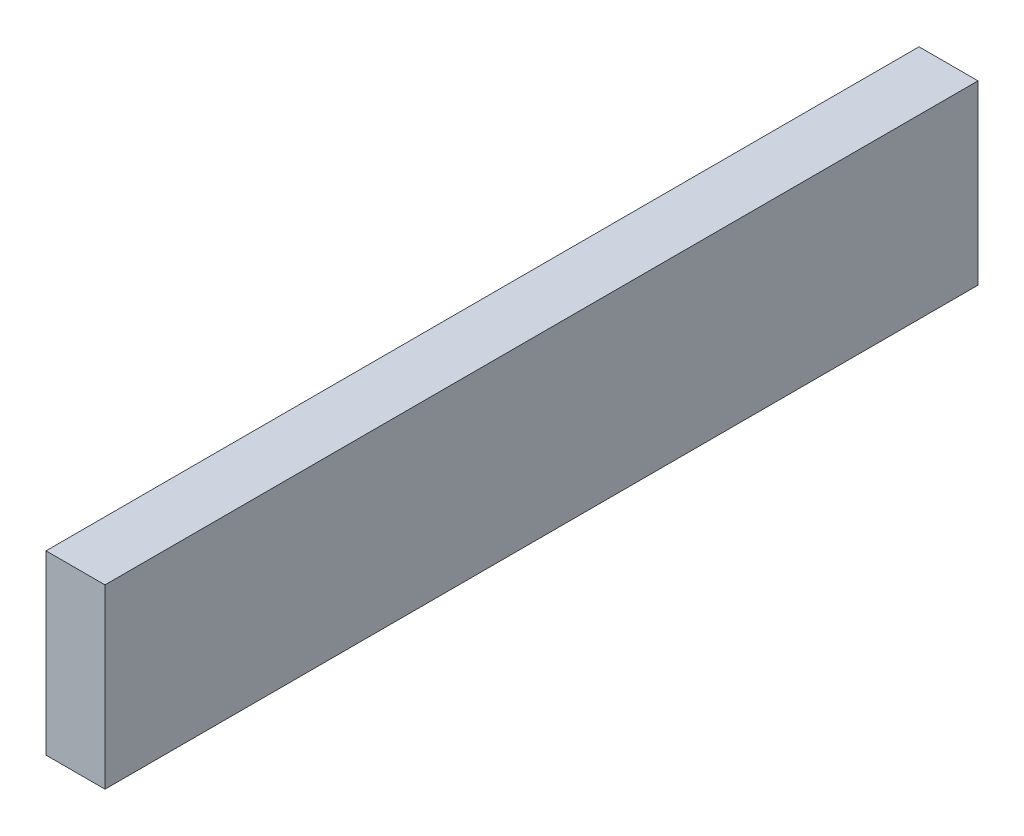
SolidWorks part; units mm, degrees
ref_plane "Front Plane" through (0, 0, 0) normal (0, 0, 1) x (1, 0, 0)
ref_plane "Top Plane" through (0, 0, 0) normal (0, 1, 0) x (1, 0, 0)
ref_plane "Right Plane" through (0, 0, 0) normal (1, 0, 0) x (0, 0, -1)
sketch "Sketch1" plane through (0, 0, 0) normal (0, 0, 1) x (1, 0, 0)
  line L1 (-7.5, 10) -> (7.5, 10)
  line L2 (-7.5, 10) -> (-7.5, -10)
  line L3 (-7.5, -10) -> (7.5, -10)
  line L4 (7.5, 10) -> (7.5, -10)
  line L5 (-7.5, 10) -> (7.5, -10) construction
  line L6 (-7.5, -10) -> (7.5, 10) construction
  point P0 (0, 0)
  dimension "D1" = 15
  dimension "D2" = 20
extrude "Boss-Extrude1" add sketch "Sketch1" along normal blind 230
sketch "Sketch2" plane through (0, 0, 0) normal (0, 0, -1) x (-1, 0, 0)
  line L1 (-32.5, 10) -> (32.5, 10)
  line L2 (-32.5, 10) -> (-32.5, 50)
  line L3 (-32.5, 50) -> (32.5, 50)
  line L4 (32.5, 10) -> (32.5, 50)
  line L6 (-7.5, 10) -> (7.5, 10) construction
  point P4 (0, 10)
  point P10 (0, 10)
  dimension "D1" = 65
  dimension "D2" = 40
extrude "Boss-Extrude6" add sketch "Sketch2" against normal blind 5 separate body
sketch "Sketch7" plane through (32.5, 0, 0) normal (1, 0, 0) x (0, 0, -1)
  line L0 (0, 50) -> (0, 10) construction
  line L1 (0, 37.5) -> (-74, 37.5)
  line L2 (0, 37.5) -> (0, 22.5)
  line L3 (0, 22.5) -> (-74, 22.5)
  line L4 (-74, 37.5) -> (-74, 22.5)
  point P4 (0, 30)
  point P7 (0, 30)
  dimension "D1" = 15
  dimension "D2" = 74
extrude "Boss-Extrude7" add sketch "Sketch7" along normal blind 5 separate body
sketch "Sketch8" plane through (-32.5, 0, 0) normal (-1, 0, 0) x (0, 0, 1)
  line L1 (0, 37.5) -> (74, 37.5)
  line L2 (0, 37.5) -> (0, 22.5)
  line L3 (0, 22.5) -> (74, 22.5)
  line L4 (74, 37.5) -> (74, 22.5)
extrude "Boss-Extrude8" add sketch "Sketch8" along normal blind 5 separate body
sketch "Sketch9" plane through (0, 0, 74) normal (0, 0, 1) x (1, 0, 0)
  line L1 (-32.5, 50) -> (32.5, 50)
  line L2 (-32.5, 50) -> (-32.5, 10)
  line L3 (-32.5, 10) -> (32.5, 10)
  line L4 (32.5, 50) -> (32.5, 10)
extrude "Boss-Extrude11" add sketch "Sketch9" against normal blind 5 separate body
sketch "Sketch10" plane through (-7.5, 0, 0) normal (-1, 0, 0) x (0, 0, 1)
  line L0 (230, 10) -> (230, -10) construction
  line L2 (209.8431, 2) -> (211.3431, 2)
  line L3 (209.8431, 2) -> (209.8431, -2)
  line L4 (209.8431, -2) -> (211.3431, -2)
  line L6 (209.8431, 2) -> (211, 0) construction
  line L7 (209.8431, -2) -> (211, 0) construction
  arc A0 (211.3431, -2) -> (211.3431, 2) centre (217, 0) ccw
  point P4 (230, 0)
  point P5 (211, 0)
  point P11 (209.8431, 0)
  dimension "D1" = 12
  dimension "D2" = 13
  dimension "D3" = 1.5
  dimension "D4" = 4
extrude "Cut-Extrude1" cut sketch "Sketch10" against normal through all
delete or keep bodies "Body-Delete/Keep 4" type delete bodies bodies 106 108 109 110
